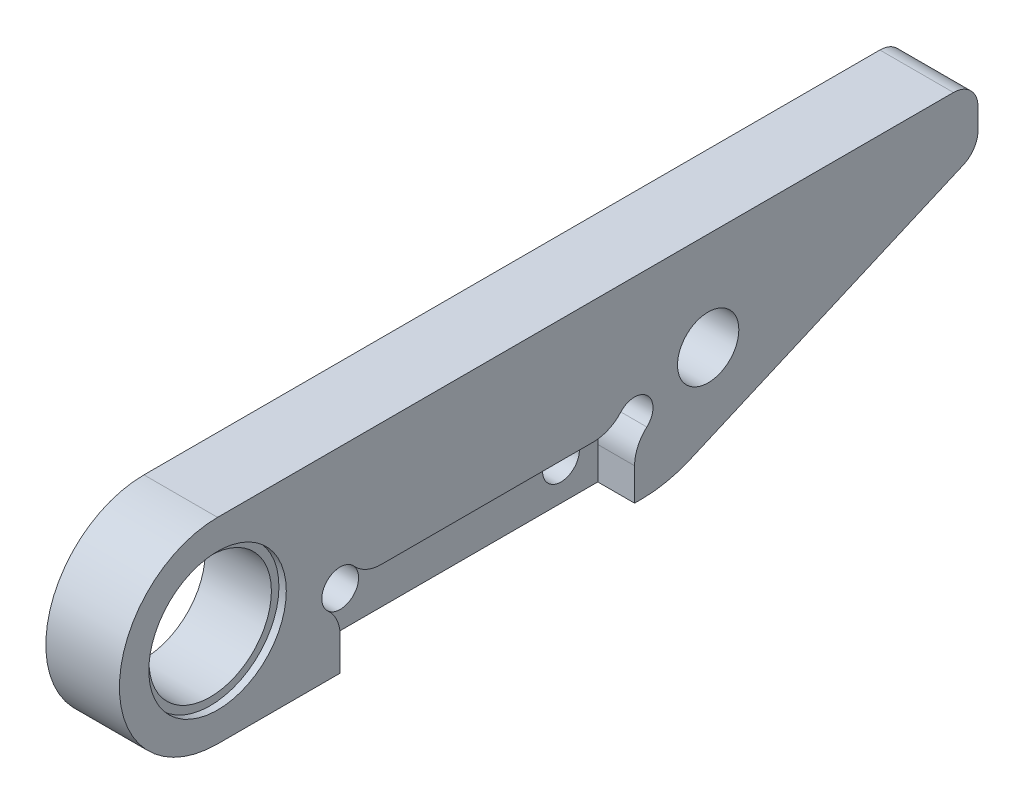
SolidWorks part; units mm, degrees
material "1060 Alloy"
ref_plane "Front Plane" through (0, 0, 0) normal (0, 0, 1) x (1, 0, 0)
ref_plane "Top Plane" through (0, 0, 0) normal (0, 1, 0) x (1, 0, 0)
ref_plane "Right Plane" through (0, 0, 0) normal (1, 0, 0) x (0, 0, -1)
sketch "Sketch27" plane through (0, 0, 0) normal (1, 0, 0) x (0, 0, -1)
  line L2 (10, 50) -> (72, 50)
  line L3 (10, 42) -> (31.9317, 42) construction
  line L4 (31.9317, 42) -> (31.9317, 54) construction
  line L6 (10, 34) -> (46.6326, 34)
  line L7 (31.9317, 54) -> (10, 42) construction
  line L8 (0, 0) -> (60, 0) construction
  line L9 (0, 0) -> (0, 58) construction
  line L10 (0, 58) -> (60, 58) construction
  line L11 (60, 0) -> (60, 58) construction
  line L12 (72, 50) -> (72, 45)
  line L13 (46.6326, 34) -> (72, 45)
  arc A0 (10, 50) -> (10, 34) centre (10, 42) ccw
  circle A1 centre (50, 42) radius 6 construction
  circle A3 centre (10, 42) radius 5.6 construction
  circle A5 centre (10, 42) radius 4.99
  circle A6 centre (50, 42) radius 2.5
  dimension "D9" = 12
  dimension "D10" = 5
  dimension "D12" = 9.98
  dimension "D13" = 8
  dimension "D14" = 5
  dimension "D6" = 22
  dimension "D16" = 11.2
  dimension "D1" = 60
  dimension "D2" = 58
  dimension "D3" = 42
  dimension "D4" = 10
  dimension "D5" = 50
  dimension "D7" = 42
  dimension "D8" = 12
  dimension "D17" = 25
extrude "Boss-Extrude1" add sketch "Sketch27" along normal blind 6
sketch "Sketch33" plane through (6, 0, 0) normal (1, 0, 0) x (0, 0, -1)
  circle A0 centre (10, 42) radius 5.605
  dimension "D1" = 11.21
extrude "Cut-Extrude2" cut sketch "Sketch33" against normal blind 0.6
sketch "Sketch34" plane through (6, 0, 0) normal (1, 0, 0) x (0, 0, -1)
  line L0 (20, 34) -> (44, 34)
  line L1 (20, 34) -> (20, 40)
  line L2 (44, 34) -> (44, 40)
  line L3 (20, 40) -> (44, 40)
  line L4 (10, 34) -> (46.6326, 34) construction
  circle A0 centre (50, 42) radius 2.5 construction
  dimension "D1" = 24
  dimension "D2" = 6
  dimension "D3" = 6
extrude "Cut-Extrude3" cut sketch "Sketch34" against normal blind 3
sketch "Sketch35" plane through (6, 0, 0) normal (1, 0, 0) x (0, 0, -1)
  circle A0 centre (20, 40) radius 1.5
  circle A1 centre (44, 40) radius 1.5
  dimension "D1" = 3
extrude "Cut-Extrude4" cut sketch "Sketch35" against normal up to surface (3 mm away) up to face at (3, 37, -32)
fillet "Fillet1" radius 3 4 edges at (4.5, 38.5, -44) (4.5, 40, -42.5) (4.5, 38.5, -20) (4.5, 40, -21.5)
sketch "Sketch36" plane through (3, 0, 0) normal (1, 0, 0) x (0, 0, -1)
  line L0 (20, 36.6459) -> (20, 34) construction
  line L1 (20, 34) -> (44, 34) construction
  line L2 (44, 34) -> (44, 36.6459) construction
  circle A0 centre (23, 37) radius 1.5
  circle A1 centre (41, 37) radius 1.5
  dimension "D1" = 3
  dimension "D2" = 3
  dimension "D3" = 3
  dimension "D4" = 3
  dimension "D5" = 3
extrude "Cut-Extrude5" cut sketch "Sketch36" against normal up to next
fillet "Fillet3" radius 2 2 edges at (3, 50, -72) (3, 45, -72)
fillet "Fillet4" radius 10 1 edges at (3, 34, -46.6326)
